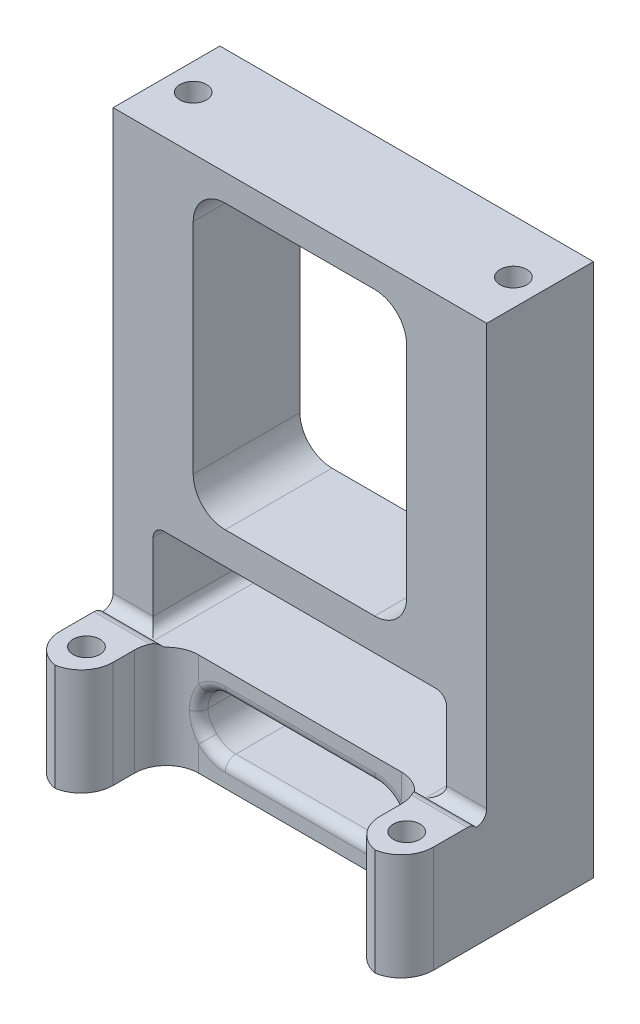
SolidWorks part; units mm, degrees
ref_plane "Front" through (0, 0, 0) normal (0, 0, 1) x (1, 0, 0)
ref_plane "Top" through (0, 0, 0) normal (0, 1, 0) x (1, 0, 0)
ref_plane "Right" through (0, 0, 0) normal (1, 0, 0) x (0, 0, -1)
sketch "Эскиз1" plane through (0, 0, 0) normal (0, 0, 1) x (1, 0, 0)
  line L1 (-8, 4.2) -> (8, 4.2)
  line L2 (-8, 4.2) -> (-8, -4.2)
  line L3 (-8, -4.2) -> (8, -4.2)
  line L4 (8, 4.2) -> (8, -4.2)
  line L7 (-17.5, 36.2) -> (17.5, 36.2)
  line L8 (-17.5, 36.2) -> (-17.5, -13.8)
  line L9 (-17.5, -13.8) -> (17.5, -13.8)
  line L10 (17.5, 36.2) -> (17.5, -13.8)
  point P0 (0, -4.2)
  point P15 (8, 0)
  point P17 (0, -13.8)
  dimension "D1" = 8.4
  dimension "D2" = 16
  dimension "D3" = 50
  dimension "D4" = 35
  dimension "D5" = 9.6
extrude "Основа" add sketch "Эскиз1" along normal mid plane 10
sketch "Эскиз2" plane through (0, 0, 5) normal (0, 0, 1) x (1, 0, 0)
  line L0 (0, 4.2) -> (0, -4.2) construction
  line L1 (8, 4.2) -> (-8, 4.2) construction
  line L2 (-8, -4.2) -> (8, -4.2) construction
  line L3 (-8, 4.2) -> (-8, -4.2) construction
  line L4 (-13.75, 4.2) -> (-8, 4.2)
  line L5 (-13.75, 4.2) -> (-13.75, -4.2)
  line L6 (-13.75, -4.2) -> (-8, -4.2)
  line L7 (-8, 4.2) -> (-8, -4.2)
  line L8 (13.75, -4.2) -> (8, -4.2)
  line L9 (8, 4.2) -> (8, -4.2)
  line L10 (13.75, 4.2) -> (8, 4.2)
  line L11 (13.75, 4.2) -> (13.75, -4.2)
  dimension "D2" = 5.75
extrude "Под ушки разъема" cut sketch "Эскиз2" against normal offset from surface (8.5 mm away) 1.5 up to face at (0, 11.2, -5)
fillet "Скругление1" radius 1 4 edges at (-13.75, -4.2, 0.75) (-13.75, 4.2, 0.75) (13.75, -4.2, 0.75) (13.75, 4.2, 0.75)
sketch "Эскиз3" plane through (0, 0, -3.5) normal (0, 0, 1) x (1, 0, 0)
  line L0 (10.3, 0) -> (-10.3, 0) construction
  circle A0 centre (-10.3, 0) radius 1.25
  circle A1 centre (10.3, 0) radius 1.25
  point P4 (0, 0)
  dimension "D1" = 2.5
  dimension "D2" = 20.6
extrude "Под шурупы крепления разъема" cut sketch "Эскиз3" against normal blind 8
sketch "Эскиз10" plane through (0, -13.8, 0) normal (0, -1, 0) x (1, 0, 0)
  line L0 (15, 0) -> (-15, 0) construction
  line L1 (-17.5, 5) -> (-17.5, -5) construction
  circle A0 centre (-15, 0) radius 1.25
  circle A1 centre (15, 0) radius 1.25
  point P4 (0, 0)
  point P9 (-17.5, 0)
  dimension "D1" = 2.5
  dimension "D2" = 30
extrude "Отверстия под шурупы снизу" cut sketch "Эскиз10" against normal blind 10
ref_plane "Средняя перпендикулярная" through (0, 11.2, 0) normal (0, 1, 0) x (1, 0, 0)
mirror "Отверстия под шурупы сверху" about plane through (0, 11.2, 0) normal (0, 1, 0) of "Отверстия под шурупы снизу"
sketch "Эскиз11" plane through (0, 0, 5) normal (0, 0, 1) x (1, 0, 0)
  line L0 (-10, 7.2) -> (-10, 33.7)
  line L1 (-10, 33.7) -> (10, 33.7)
  line L2 (10, 33.7) -> (10, 7.2)
  line L3 (10, 7.2) -> (-10, 7.2)
  line L4 (17.5, 36.2) -> (-17.5, 36.2) construction
  line L5 (12.75, 4.2) -> (-12.75, 4.2) construction
  point P2 (0, 33.7)
  point P7 (0, 36.2)
  dimension "D1" = 20
  dimension "D2" = 2.5
  dimension "D3" = 3
extrude "Окошко по центру" cut sketch "Эскиз11" against normal through all
fillet "Скругление2" radius 3 4 edges at (-10, 33.7, 0) (10, 33.7, 0) (10, 7.2, 0) (-10, 7.2, 0)
sketch "Эскиз12" [suppressed] plane through (0, 0, 5) normal (0, 0, 1) x (1, 0, 0)
  line L0 (-1.9304, 22.3017) -> (-1.9304, 18.2765)
  line L1 (-1.9304, 18.2765) -> (-4.7378, 18.2765)
  line L2 (-4.7378, 18.2765) -> (-7.0799, 20.9081)
  line L3 (-7.0799, 20.9081) -> (-7.0799, 21.072)
  line L4 (-7.7539, 8.4789) -> (-22.5, 8.4789)
  line L5 (-8.9739, 23.061) -> (-9.605, 23.409)
  line L6 (-9.605, 23.409) -> (-10.3399, 24.3315)
  line L7 (-10.3399, 24.3315) -> (-10.3399, 25.2031)
  line L8 (-10.3399, 25.2031) -> (-12.1829, 28.4959)
  line L9 (-12.1829, 28.4959) -> (-12.5, 28.5884)
  line L10 (-12.5, 28.5884) -> (-12.5, 32.7222)
  line L11 (-12.5, 32.7222) -> (-22.5, 32.7222)
  line L12 (-22.5, 32.7222) -> (-22.5, 29.9118)
  line L13 (-22.5, 29.9118) -> (-16.9631, 28.297)
  line L14 (-16.9631, 28.297) -> (-15.3014, 25.3281)
  line L15 (-15.3014, 25.3281) -> (-15.3014, 24.4969)
  line L16 (-15.3014, 24.4969) -> (-14.2291, 23.1507)
  line L17 (-14.2291, 23.1507) -> (-14.029, 23.0404)
  line L18 (-14.029, 23.0404) -> (-12.5691, 21.5073)
  line L19 (-12.5691, 21.5073) -> (-12.5691, 18.2465)
  line L20 (-12.5691, 18.2465) -> (-8.2558, 13.4)
  line L21 (-8.2558, 13.4) -> (-7.7539, 13.4)
  line L22 (-7.7539, 13.4) -> (-7.7539, 8.4789)
  line L23 (-22.5, 43.8) -> (-22.5, -6.2) construction
  line L24 (0, 25.805) -> (0, 0) construction
  line L25 (7.7539, 13.4) -> (7.7539, 8.4789)
  line L26 (8.2558, 13.4) -> (7.7539, 13.4)
  line L27 (12.5691, 18.2465) -> (8.2558, 13.4)
  line L28 (12.5691, 21.5073) -> (12.5691, 18.2465)
  line L29 (14.029, 23.0404) -> (12.5691, 21.5073)
  line L30 (14.2291, 23.1507) -> (14.029, 23.0404)
  line L31 (15.3014, 24.4969) -> (14.2291, 23.1507)
  line L32 (15.3014, 25.3281) -> (15.3014, 24.4969)
  line L33 (16.9631, 28.297) -> (15.3014, 25.3281)
  line L34 (22.5, 29.9118) -> (16.9631, 28.297)
  line L35 (22.5, 32.7222) -> (22.5, 29.9118)
  line L36 (12.5, 32.7222) -> (22.5, 32.7222)
  line L37 (12.5, 28.5884) -> (12.5, 32.7222)
  line L38 (12.1829, 28.4959) -> (12.5, 28.5884)
  line L39 (10.3399, 25.2031) -> (12.1829, 28.4959)
  line L40 (10.3399, 24.3315) -> (10.3399, 25.2031)
  line L41 (9.605, 23.409) -> (10.3399, 24.3315)
  line L42 (8.9739, 23.061) -> (9.605, 23.409)
  line L43 (7.7539, 8.4789) -> (22.5, 8.4789)
  line L44 (7.0799, 20.9081) -> (7.0799, 21.072)
  line L45 (4.7378, 18.2765) -> (7.0799, 20.9081)
  line L46 (1.9304, 18.2765) -> (4.7378, 18.2765)
  line L47 (1.9304, 22.3017) -> (1.9304, 18.2765)
  line L49 (-22.5, 29.9118) -> (-22.5, 8.4789)
  line L51 (22.5, 29.9118) -> (22.5, 8.4789)
  line L53 (12.5, 32.7222) -> (12.5, 43.8)
  line L54 (22.5, 43.8) -> (-22.5, 43.8) construction
  line L55 (12.5, 43.8) -> (-12.5, 43.8)
  line L56 (-12.5, 43.8) -> (-12.5, 32.7222)
  circle A0 centre (0, 25.805) radius 4
  arc A1 (-7.0799, 21.072) -> (-8.9739, 23.061) centre (-8.53, 21.5875) ccw
  arc A2 (7.0799, 21.072) -> (8.9739, 23.061) centre (8.53, 21.5875) cw
  line M52 (22.5, -6.2) -> (22.5, 43.8)
  line M53 (22.5, 43.8) -> (-22.5, 43.8)
  line M54 (-22.5, 43.8) -> (-22.5, -6.2)
  dimension "D1" = 8
  dimension "D2" = 10
extrude "Силач!" [suppressed] cut sketch "Эскиз12" against normal through all contours L22 L21 L20 L19 L18 L17 L16 L15 L14 L13 L4 M54 | L25 L43 L34 L33 L32 L31 L30 L29 L28 L27 L26 M52 | L44 A2 L42 L41 L40 L39 L38 L37 L53 L56 L10 L9 L8 L7 L6 L5 A1 L3 L2 L1 L0 A0 L47 L46 L45 M53
sketch "Эскиз13" plane through (0, -13.8, 0) normal (0, -1, 0) x (1, 0, 0)
  line L0 (-17.5, 5) -> (-17.5, 13)
  line L1 (-17.5, 5) -> (17.5, 5) construction
  line L2 (-17.5, 13) -> (-12.5, 13)
  line L4 (0, 5) -> (0, -5) construction
  line L5 (-17.5, -5) -> (17.5, -5) construction
  line L6 (-17.5, 5) -> (-12.5, 5)
  line L7 (17.5, 5) -> (12.5, 5)
  line L8 (12.5, 13) -> (12.5, 5)
  line L9 (17.5, 13) -> (12.5, 13)
  line L10 (17.5, 5) -> (17.5, 13)
  line L11 (-12.5, 5) -> (-12.5, 13)
  point P15 (-15, 13)
  point P17 (15, 13)
  dimension "D1" = 5
  dimension "D2" = 30
  dimension "D3" = 8
extrude "Уши для крепления платы" add sketch "Эскиз13" against normal blind 9.6
sketch "Эскиз16" plane through (0, -4.2, 0) normal (0, 1, 0) x (1, 0, 0)
  line L3 (0, 0) -> (0, -5) construction
  line L4 (17.5, -5) -> (-17.5, -5) construction
  line L6 (-17.5, -6) -> (-12.5, -6)
  line L7 (-17.5, -6) -> (-17.5, -13)
  line L8 (-17.5, -13) -> (-12.5, -13)
  line L9 (-12.5, -6) -> (-12.5, -13)
  line L10 (-17.5, -5) -> (-17.5, -13) construction
  line L11 (17.5, -13) -> (12.5, -13)
  line L12 (12.5, -6) -> (12.5, -13)
  line L13 (17.5, -6) -> (12.5, -6)
  line L14 (17.5, -6) -> (17.5, -13)
  dimension "D1" = 7
extrude "Наплывы под плату" add sketch "Эскиз16" along normal blind 0.4
sketch "Эскиз14" plane through (0, -3.8, 0) normal (0, 1, 0) x (1, 0, 0)
  line L0 (0, 0) -> (0, -5) construction
  line L1 (17.5, -5) -> (-17.5, -5) construction
  line L5 (-12.5, -5) -> (12.5, -5) construction
  circle A0 centre (-15, -10) radius 1.25
  circle A2 centre (15, -10) radius 1.25
  dimension "D1" = 2.5
  dimension "D2" = 5
  dimension "D3" = 30
extrude "Для крепления платы" cut sketch "Эскиз14" against normal through all
fillet "Скругление3" radius 3 6 edges at (17.5, -8.8, 13) (12.5, -8.8, 13) (-17.5, -8.8, 13) (12.5, -9, 5) (-12.5, -9, 5) (-12.5, -8.8, 13)
fillet "Скругление4" radius 1 2 edges at (15.125, -4.2, 5) (-15.125, -4.2, 5)
fillet "Скругление5" radius 1 2 edges at (14.618, -3.8, 6) (-14.618, -3.8, 6)
sketch "Эскиз17" plane through (0, 0, 5) normal (0, 0, 1) x (1, 0, 0)
  line L1 (-9.5, -11.5) -> (9.5, -11.5)
  line L2 (-9.5, -11.5) -> (-9.5, -6.5)
  line L3 (-9.5, -6.5) -> (9.5, -6.5)
  line L4 (9.5, -11.5) -> (9.5, -6.5)
  line L6 (-9.5, -4.2) -> (-9.5, -13.8) construction
  line L7 (9.5, -13.8) -> (9.5, -4.2) construction
  point P9 (-9.5, -9)
  point P10 (-9.5, -9)
  dimension "D1" = 5
extrude "Окошко снизу" cut sketch "Эскиз17" against normal up to next
fillet "Скругление6" radius 2.5 4 edges at (9.5, -6.5, 0) (9.5, -11.5, 0) (-9.5, -6.5, 0) (-9.5, -11.5, 0)
fillet "Скругление7" radius 1 12 edges at (8.7678, -7.2322, 5) (8.7678, -10.7678, 5) (0, -11.5, 5) (-8.7678, -10.7678, 5) (-8.7678, -7.2322, 5) (0, -6.5, 5) (0, -11.5, -5) (-8.7678, -10.7678, -5) (-8.7678, -7.2322, -5) (0, -6.5, -5) (8.7678, -7.2322, -5) (8.7678, -10.7678, -5)
